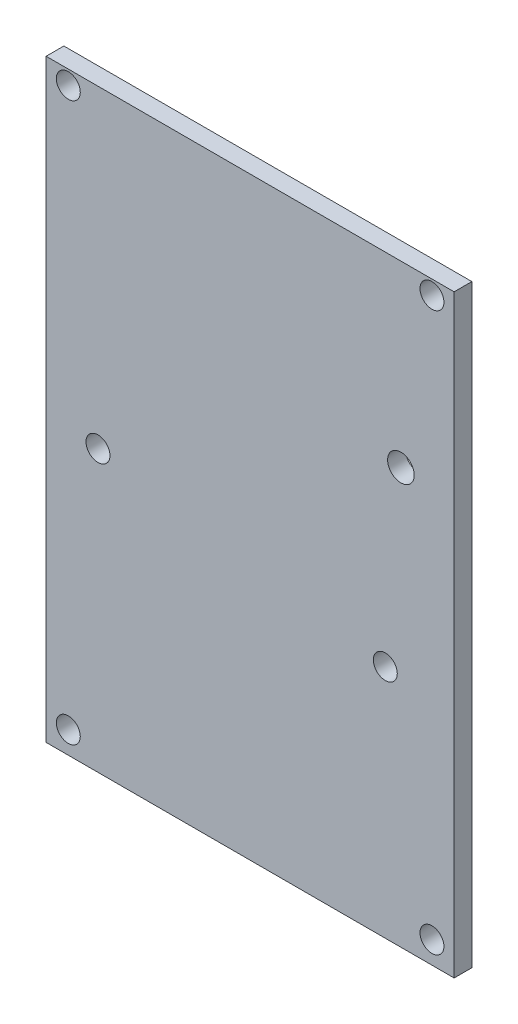
SolidWorks part; units mm, degrees
ref_plane "Front Plane" through (0, 0, 0) normal (0, 0, 1) x (1, 0, 0)
ref_plane "Top Plane" through (0, 0, 0) normal (0, 1, 0) x (1, 0, 0)
ref_plane "Right Plane" through (0, 0, 0) normal (1, 0, 0) x (0, 0, -1)
sketch "Sketch1" plane through (0, 0, 0) normal (0, 0, 1) x (1, 0, 0)
  line L1 (-23, -33.5) -> (23, -33.5)
  line L2 (-23, -33.5) -> (-23, 33.5)
  line L3 (-23, 33.5) -> (23, 33.5)
  line L4 (23, -33.5) -> (23, 33.5)
  line L5 (-23, -33.5) -> (23, 33.5) construction
  line L6 (-23, 33.5) -> (23, -33.5) construction
  point P0 (0, 0)
  dimension "D1" = 46
  dimension "D2" = 67
extrude "Boss-Extrude1" add sketch "Sketch1" along normal blind 2
hole_wizard "Ø2.7 (2.7) Diameter Hole1" positions "Sketch2" profile "Sketch3" hole size "Ø2.7" standard "DIN" end condition through all
sketch "Sketch2" plane through (0, 0, 2) normal (0, 0, 1) x (1, 0, 0)
  line L1 (-23, -33.5) -> (23, -33.5) construction
  line L2 (-23, 33.5) -> (-23, -33.5) construction
  line L5 (23, 33.5) -> (-23, 33.5) construction
  point P0 (-20.5, 31.9)
  point P2 (20.5, 31.9)
  point P4 (20.5, -31)
  point P6 (-20.5, -31)
  point P8 (-17.155, -1.895)
  point P10 (15.24, -6.985)
  point P41 (0, 0)
  point P47 (0, 0)
  dimension "D1" = 41
  dimension "D2" = 41
  dimension "D3" = 2.5
  dimension "D4" = 2.5
  dimension "D5" = 1.6
  dimension "D6" = 22.605
  dimension "D7" = 0.155
  dimension "D8" = 17.515
  dimension "D9" = 1.76
sketch "Sketch3" plane through (-20.5, 31.9, 2) normal (1, 0, 0) x (0, -1, 0)
  line L0 (0, 0) -> (0, 2)
  line L1 (0, 2) -> (1.35, 2)
  line L2 (1.35, 2) -> (1.35, 0)
  line L5 (1.35, 0) -> (0, 0)
  line L11 (0, -6.35) -> (0, 107.95) construction
  dimension "Thru Hole Dia." = 2.7
  dimension "Thru Hole Depth" = 2
hole_wizard "Ø3.0 (3) Diameter Hole1" positions "Sketch4" profile "Sketch5" hole size "Ø3.0" standard "DIN" end condition through all
sketch "Sketch4" plane through (0, 0, 2) normal (0, 0, 1) x (1, 0, 0)
  point P0 (17, 13.345)
  dimension "D1" = 37.845
sketch "Sketch5" plane through (17, 13.345, 2) normal (1, 0, 0) x (0, -1, 0)
  line L0 (0, 0) -> (0, 2)
  line L1 (0, 2) -> (1.5, 2)
  line L2 (1.5, 2) -> (1.5, 0)
  line L5 (1.5, 0) -> (0, 0)
  line L11 (0, -6.35) -> (0, 107.95) construction
  dimension "Thru Hole Dia." = 3
  dimension "Thru Hole Depth" = 2
equation "\"D1@Fillet5\"=\"D1@Fillet1\""
equation "\"D4@Hole locations\" = \"D3@Hole locations\""
equation "\"SubD9HoleLeft\"=10.5"
equation "\"D3@Sketch58\"=\"SubD9HoleLeft\""
equation "\"TopHoleLocFromTop\"=1.6"
equation "\"D1@Hole locations\"=\"TopHoleLocFromTop\""
equation "\"D5@Sketch2\"=\"TopHoleLocFromTop\""
